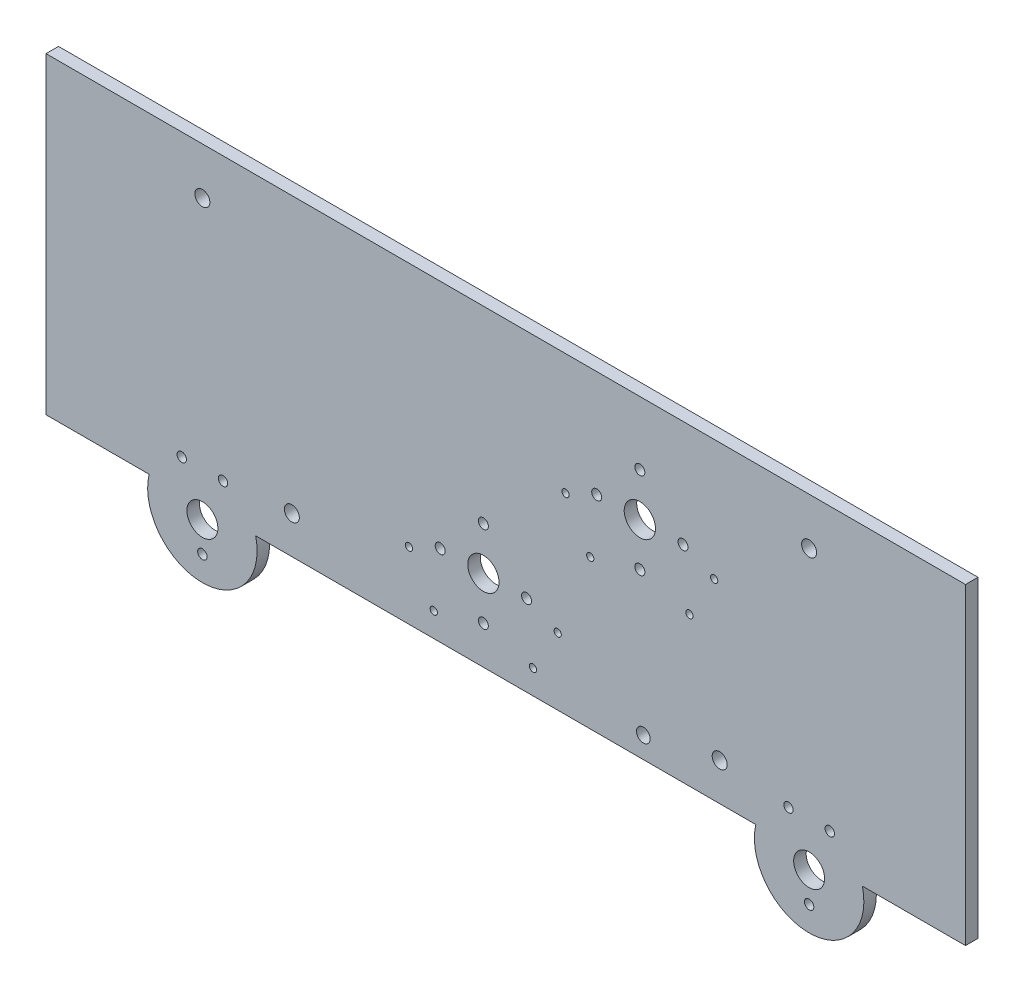
SolidWorks part; units mm, degrees
ref_plane "Front Plane" through (0, 0, 0) normal (0, 0, 1) x (1, 0, 0)
ref_plane "Top Plane" through (0, 0, 0) normal (0, 1, 0) x (1, 0, 0)
ref_plane "Right Plane" through (0, 0, 0) normal (1, 0, 0) x (0, 0, -1)
sketch "Sketch2" plane through (0, 0, 0) normal (0, 0, 1) x (1, 0, 0)
  line L0 (-123.19, -36.83) -> (-123.19, -31.75) construction
  line L1 (-186.69, -31.75) -> (186.69, -31.75)
  line L2 (-186.69, -31.75) -> (-186.69, 31.75)
  line L3 (-186.69, 31.75) -> (186.69, 31.75)
  line L4 (186.69, -31.75) -> (186.69, 31.75)
  line L5 (-186.69, -31.75) -> (186.69, 31.75) construction
  line L6 (-186.69, 31.75) -> (186.69, -31.75) construction
  line L7 (0, 0) -> (0, -31.75) construction
  line L8 (123.19, -36.83) -> (123.19, -31.75) construction
  line L16 (-186.69, 31.75) -> (186.69, 31.75)
  line L17 (-186.69, 31.75) -> (-186.69, 95.25)
  line L18 (-186.69, 95.25) -> (186.69, 95.25)
  line L19 (186.69, 31.75) -> (186.69, 95.25)
  circle A0 centre (-123.19, -36.83) radius 6.2865
  circle A1 centre (123.19, -36.83) radius 6.2865
  circle A2 centre (-123.19, -36.83) radius 22.225
  circle A3 centre (123.19, -36.83) radius 22.225
  circle A4 centre (-123.19, 76.2) radius 3.048
  circle A5 centre (123.19, 76.2) radius 3.048
  circle A7 centre (86.868, -16.51) radius 3.048
  circle A8 centre (-86.868, -16.51) radius 3.048
  point P0 (0, 0)
  point P27 (-86.868, -16.51)
  dimension "D3" = 123.19
  dimension "D5" = 5.08
  dimension "D7" = 63.5
  dimension "D8" = 44.45
  dimension "D4" = 12.573
  dimension "D9" = 12.573
  dimension "D10" = 44.45
  dimension "D13" = 6.096
  dimension "D14" = 6.096
  dimension "D19" = 6.096
  dimension "D20" = 6.096
  dimension "D1" = 63.5
  dimension "D2" = 373.38
  dimension "D6" = 123.19
  dimension "D11" = 107.95
  dimension "D12" = 107.95
  dimension "D15" = 86.868
  dimension "D16" = 15.24
  dimension "D17" = 15.24
  dimension "D18" = 86.868
extrude "Boss-Extrude1" add sketch "Sketch2" against normal blind 5.0749 contours A1 L1 L4 L3 L2 A0 | L3 L19 L18 L17 | A2 | A3 region at (0, 1.2473, 0) region at (0, 63.4687, 0)
extrude "Cut-Extrude11" cut sketch "Sketch2<4>" against normal through all contours L1 A0 | L1 A1 | A0 | A1 region at (-123.19, -37.1167, 0) region at (123.19, -37.1167, 0)
sketch "Sketch2<4>" plane through (0, 0, 0) normal (0, 0, 1) x (1, 0, 0) same geometry as "Sketch2"
ref_plane "Plane1" through (-186.69, 95.25, 0) normal (0, 1, 0) x (1, 0, 0)
ref_plane "Plane2" through (0, 0, -5.0749) normal (0, 0, -1) x (-1, 0, 0)
sketch "Sketch3" plane through (0, 0, 0) normal (0, 0, 1) x (1, 0, 0)
  line L0 (-101.5534, -31.75) -> (101.5534, -31.75) construction
  circle A0 centre (-9.0908, 1.27) radius 22.86
  circle A1 centre (54.4505, 51.9547) radius 22.86
  circle A2 centre (-9.0908, 1.27) radius 6.35
  circle A3 centre (54.4505, 51.9547) radius 6.35
  circle A4 centre (-26.6168, 1.27) radius 2.032
  circle A5 centre (-9.0908, 18.796) radius 2.032
  circle A6 centre (-9.0908, -16.256) radius 2.032
  circle A7 centre (8.4352, 1.27) radius 2.032
  circle A8 centre (36.9245, 51.9547) radius 2.032
  circle A9 centre (71.9765, 51.9547) radius 2.032
  circle A10 centre (54.4505, 69.4807) radius 2.032
  circle A11 centre (54.4505, 34.4287) radius 2.032
  point P0 (-9.0908, 1.27)
  point P1 (54.4505, 51.9547)
  dimension "D5" = 45.72
  dimension "D6" = 12.7
  dimension "D7" = 12.7
  dimension "D12" = 4.064
  dimension "D15" = 4.064
  dimension "D2" = 120.2923
  dimension "D3" = 112.2846
  dimension "D4" = 81.28
  dimension "D8" = 17.526
  dimension "D9" = 17.526
  dimension "D10" = 17.526
  dimension "D11" = 17.526
  dimension "D13" = 17.526
  dimension "D14" = 17.526
  dimension "D16" = 17.526
  dimension "D17" = 17.526
  dimension "D18" = 33.02
extrude "Cut-Extrude12" cut sketch "Sketch3" against normal through all contours A2 | A7 | A3 | A9 | A10 | A8 | A5 | A4 | A6 | A11 region at (-9.0908, 1.27, 0) region at (54.4505, 51.9547, 0) region at (8.4352, 1.27, 0) region at (36.9245, 51.9547, 0) region at (71.9765, 51.9547, 0) region at (54.4505, 69.4807, 0)
sketch "Sketch5" plane through (0, 0, 0) normal (0, 0, 1) x (1, 0, 0)
  line L0 (-9.0908, 1.27) -> (-9.0908, -29.464) construction
  line L1 (54.4505, 51.9547) -> (54.4505, 21.2207) construction
  line L2 (-39.2746, -4.5195) -> (21.093, -4.5195) construction
  line L3 (-29.2279, -21.948) -> (11.0464, -21.948) construction
  line L4 (34.3134, 28.7367) -> (74.5877, 28.7367) construction
  line L5 (24.2668, 46.1652) -> (84.6343, 46.1652) construction
  circle A0 centre (-9.0908, 1.27) radius 30.734
  circle A1 centre (54.4505, 51.9547) radius 30.734
  circle A2 centre (-29.2279, -21.948) radius 1.4732
  circle A3 centre (11.0464, -21.948) radius 1.4732
  circle A4 centre (-39.2746, -4.5195) radius 1.4732
  circle A5 centre (21.093, -4.5195) radius 1.4732
  circle A6 centre (34.3134, 28.7367) radius 1.4732
  circle A7 centre (74.5877, 28.7367) radius 1.4732
  circle A8 centre (24.2668, 46.1652) radius 1.4732
  circle A9 centre (84.6343, 46.1652) radius 1.4732
  circle A10 centre (-9.0908, -29.464) radius 1.4732
  circle A11 centre (54.4505, 21.2207) radius 1.4732
  dimension "D1" = 61.468
  dimension "D2" = 61.468
  dimension "D5" = 2.9464
  dimension "D8" = 2.9464
  dimension "D3" = 21.4941
  dimension "D4" = 20.1168
  dimension "D6" = 21.4941
  dimension "D7" = 20.1168
extrude "Cut-Extrude13" cut sketch "Sketch5" against normal through all contours A1 A8 | A1 A8 | A1 A9 | A1 A9 | A1 A7 | A4 | A2 | A3 | A5 | A6 | A7 region at (24.887, 46.2842, 0) region at (23.659, 46.0486, 0) region at (85.2421, 46.0486, 0) region at (84.0141, 46.2842, 0) region at (74.1739, 29.2139, 0)
sketch "Sketch7" plane through (0, 0, 0) normal (0, 0, 1) x (1, 0, 0)
  line L0 (-123.19, -36.83) -> (-123.19, -59.055) construction
  line L1 (-131.572, -19.05) -> (-114.808, -19.05) construction
  line L2 (123.19, -36.83) -> (123.19, -59.055) construction
  line L3 (114.808, -19.05) -> (131.572, -19.05)
  circle A0 centre (-123.19, -36.83) radius 22.225 construction
  circle A1 centre (-123.19, -49.022) radius 1.905
  circle A2 centre (-131.572, -19.05) radius 1.905
  circle A3 centre (-114.808, -19.05) radius 1.905
  circle A4 centre (123.19, -36.83) radius 22.225 construction
  circle A5 centre (123.19, -49.022) radius 1.905
  circle A6 centre (114.808, -19.05) radius 1.905
  circle A7 centre (131.572, -19.05) radius 1.905
  point P15 (-123.19, -19.05)
  point P23 (123.19, -19.05)
  dimension "D4" = 3.81
  dimension "D6" = 3.81
  dimension "D1" = 12.192
  dimension "D2" = 17.78
  dimension "D3" = 16.764
  dimension "D5" = 12.192
  dimension "D7" = 17.78
  dimension "D8" = 16.764
extrude "Cut-Extrude14" cut sketch "Sketch7" against normal through all contours A2 | A1 | A6 | A7 | A5 | A3 region at (131.572, -17.1989, 0) region at (112.9569, -19.05, 0) region at (-123.19, -49.022, 0) region at (-131.572, -19.05, 0) region at (123.19, -49.022, 0)
sketch "Sketch8" plane through (0, 0, 0) normal (0, 0, 1) x (1, 0, 0)
  line L1 (186.69, -31.75) -> (186.69, 31.75) construction
  circle A0 centre (0, -23.114) radius 3.175
  point P4 (0, 0)
  dimension "D2" = 6.35
  dimension "D1" = 8.636
  dimension "D3" = 186.69
sketch "Sketch9" plane through (0, 0, 0) normal (0, 0, 1) x (1, 0, 0)
  line L0 (-186.69, -31.75) -> (186.69, -31.75) construction
  line L1 (186.69, -31.75) -> (186.69, 31.75) construction
  circle A0 centre (55.88, -23.114) radius 2.794
  dimension "D1" = 130.81
  dimension "D2" = 8.636
extrude "Cut-Extrude16" cut sketch "Sketch9" against normal blind 5.08
